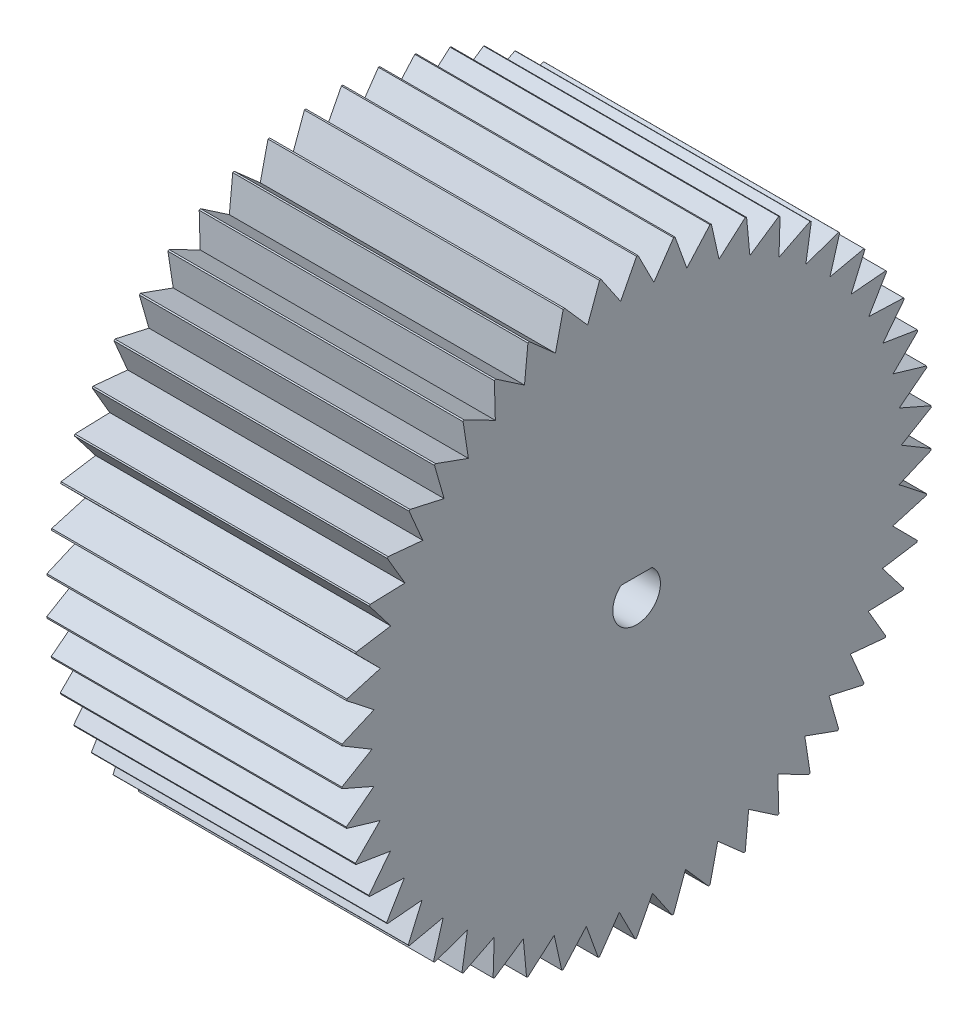
SolidWorks part; units mm, degrees
ref_plane "Front Plane" through (0, 0, 0) normal (0, 0, 1) x (1, 0, 0)
ref_plane "Top Plane" through (0, 0, 0) normal (0, 1, 0) x (1, 0, 0)
ref_plane "Right Plane" through (0, 0, 0) normal (1, 0, 0) x (0, 0, -1)
sketch "Sketch1" plane through (0, 0, 0) normal (1, 0, 0) x (0, 0, -1)
  line L0 (-3.0582, 25.2152) -> (-1.3735, 22.7329)
  line L1 (-1.3735, 22.7329) -> (0, 25.4)
  line L2 (0.1263, 25.3997) -> (1.4865, 22.7258)
  line L3 (1.4865, 22.7258) -> (3.1835, 25.1997)
  line L4 (3.3087, 25.1836) -> (4.3231, 22.3603)
  line L5 (4.3231, 22.3603) -> (6.3167, 24.602)
  line L6 (6.4389, 24.5703) -> (7.0915, 21.6421)
  line L7 (7.0915, 21.6421) -> (9.3504, 23.6163)
  line L8 (9.4676, 23.5696) -> (9.748, 20.5827)
  line L9 (9.748, 20.5827) -> (12.2365, 22.2582)
  line L10 (12.347, 22.1971) -> (12.2509, 19.1986)
  line L11 (12.2509, 19.1986) -> (14.9297, 20.549)
  line L12 (15.0317, 20.4746) -> (14.5605, 17.5118)
  line L13 (14.5605, 17.5118) -> (17.3875, 18.5158)
  line L14 (17.4793, 18.4291) -> (16.6405, 15.5488)
  line L15 (16.6405, 15.5488) -> (19.571, 16.1906)
  line L16 (19.6513, 16.0931) -> (18.4581, 13.3406)
  line L17 (18.4581, 13.3406) -> (21.4459, 13.61)
  line L18 (21.5133, 13.5032) -> (19.9845, 10.922)
  line L19 (19.9845, 10.922) -> (22.9826, 10.8148)
  line L20 (23.0361, 10.7004) -> (21.1958, 8.3311)
  line L21 (21.1958, 8.3311) -> (24.1568, 7.849)
  line L22 (24.1956, 7.7289) -> (22.0729, 5.6089)
  line L23 (22.0729, 5.6089) -> (24.9501, 4.7595)
  line L24 (24.9734, 4.6354) -> (22.6018, 2.7982)
  line L25 (22.6018, 2.7982) -> (25.3499, 1.5949)
  line L26 (25.3575, 1.4689) -> (22.7743, -0.0566)
  line L27 (22.7743, -0.0566) -> (25.3499, -1.5949)
  line L28 (25.3416, -1.7209) -> (22.5876, -2.9105)
  line L29 (22.5876, -2.9105) -> (24.9501, -4.7595)
  line L30 (24.9261, -4.8834) -> (22.0447, -5.7186)
  line L31 (22.0447, -5.7186) -> (24.1568, -7.849)
  line L32 (24.1175, -7.969) -> (21.1542, -8.4364)
  line L33 (21.1542, -8.4364) -> (22.9826, -10.8148)
  line L34 (22.9286, -10.9289) -> (19.93, -11.0212)
  line L35 (19.93, -11.0212) -> (21.4459, -13.61)
  line L36 (21.378, -13.7164) -> (18.3915, -13.4322)
  line L37 (18.3915, -13.4322) -> (19.571, -16.1906)
  line L38 (19.4903, -16.2877) -> (16.563, -15.6313)
  line L39 (16.563, -15.6313) -> (17.3875, -18.5158)
  line L40 (17.2952, -18.602) -> (14.4733, -17.584)
  line L41 (14.4733, -17.584) -> (14.9297, -20.549)
  line L42 (14.8274, -20.623) -> (12.1553, -19.2593)
  line L43 (12.1553, -19.2593) -> (12.2365, -22.2582)
  line L44 (12.1258, -22.3187) -> (9.6456, -20.6309)
  line L45 (9.6456, -20.6309) -> (9.3504, -23.6163)
  line L46 (9.2329, -23.6625) -> (6.9838, -21.6771)
  line L47 (6.9838, -21.6771) -> (6.3167, -24.602)
  line L48 (6.1944, -24.6331) -> (4.2119, -22.3815)
  line L49 (4.2119, -22.3815) -> (3.1835, -25.1997)
  line L50 (3.0582, -25.2152) -> (1.3735, -22.7329)
  line L51 (1.3735, -22.7329) -> (0, -25.4)
  line L52 (-0.1263, -25.3997) -> (-1.4865, -22.7258)
  line L53 (-1.4865, -22.7258) -> (-3.1835, -25.1997)
  line L54 (-3.3087, -25.1836) -> (-4.3231, -22.3603)
  line L55 (-4.3231, -22.3603) -> (-6.3167, -24.602)
  line L56 (-6.4389, -24.5703) -> (-7.0915, -21.6421)
  line L57 (-7.0915, -21.6421) -> (-9.3504, -23.6163)
  line L58 (-9.4676, -23.5696) -> (-9.748, -20.5827)
  line L59 (-9.748, -20.5827) -> (-12.2365, -22.2582)
  line L60 (-12.347, -22.1971) -> (-12.2509, -19.1986)
  line L61 (-12.2509, -19.1986) -> (-14.9297, -20.549)
  line L62 (-15.0317, -20.4746) -> (-14.5605, -17.5118)
  line L63 (-14.5605, -17.5118) -> (-17.3875, -18.5158)
  line L64 (-17.4793, -18.4291) -> (-16.6405, -15.5488)
  line L65 (-16.6405, -15.5488) -> (-19.571, -16.1906)
  line L66 (-19.6513, -16.0931) -> (-18.4581, -13.3406)
  line L67 (-18.4581, -13.3406) -> (-21.4459, -13.61)
  line L68 (-21.5133, -13.5032) -> (-19.9845, -10.922)
  line L69 (-19.9845, -10.922) -> (-22.9826, -10.8148)
  line L70 (-23.0361, -10.7004) -> (-21.1958, -8.3311)
  line L71 (-21.1958, -8.3311) -> (-24.1568, -7.849)
  line L72 (-24.1956, -7.7289) -> (-22.0729, -5.6089)
  line L73 (-22.0729, -5.6089) -> (-24.9501, -4.7595)
  line L74 (-24.9734, -4.6354) -> (-22.6018, -2.7982)
  line L75 (-22.6018, -2.7982) -> (-25.3499, -1.5949)
  line L76 (-25.3575, -1.4689) -> (-22.7743, 0.0566)
  line L77 (-22.7743, 0.0566) -> (-25.3499, 1.5949)
  line L78 (-25.3416, 1.7209) -> (-22.5876, 2.9105)
  line L79 (-22.5876, 2.9105) -> (-24.9501, 4.7595)
  line L80 (-24.9261, 4.8834) -> (-22.0447, 5.7186)
  line L81 (-22.0447, 5.7186) -> (-24.1568, 7.849)
  line L82 (-24.1175, 7.969) -> (-21.1542, 8.4364)
  line L83 (-21.1542, 8.4364) -> (-22.9826, 10.8148)
  line L84 (-22.9286, 10.9289) -> (-19.93, 11.0212)
  line L85 (-19.93, 11.0212) -> (-21.4459, 13.61)
  line L86 (-21.378, 13.7164) -> (-18.3915, 13.4322)
  line L87 (-18.3915, 13.4322) -> (-19.571, 16.1906)
  line L88 (-19.4903, 16.2877) -> (-16.563, 15.6313)
  line L89 (-16.563, 15.6313) -> (-17.3875, 18.5158)
  line L90 (-17.2952, 18.602) -> (-14.4733, 17.584)
  line L91 (-14.4733, 17.584) -> (-14.9297, 20.549)
  line L92 (-14.8274, 20.623) -> (-12.1553, 19.2593)
  line L93 (-12.1553, 19.2593) -> (-12.2365, 22.2582)
  line L94 (-12.1258, 22.3187) -> (-9.6456, 20.6309)
  line L95 (-9.6456, 20.6309) -> (-9.3504, 23.6163)
  line L96 (-9.2329, 23.6625) -> (-6.9838, 21.6771)
  line L97 (-6.9838, 21.6771) -> (-6.3167, 24.602)
  line L98 (-6.1944, 24.6331) -> (-4.2119, 22.3815)
  line L99 (-4.2119, 22.3815) -> (-3.1835, 25.1997)
  line L100 (-1.3416, 1.55) -> (1.3416, 1.55)
  arc A0 (-3.0582, 25.2152) -> (-3.1835, 25.1997) centre (0, 0) ccw
  arc A1 (-6.1944, 24.6331) -> (-6.3167, 24.602) centre (0, 0) ccw
  arc A2 (-9.2329, 23.6625) -> (-9.3504, 23.6163) centre (0, 0) ccw
  arc A3 (-12.1258, 22.3187) -> (-12.2365, 22.2582) centre (0, 0) ccw
  arc A4 (-14.8274, 20.623) -> (-14.9297, 20.549) centre (0, 0) ccw
  arc A5 (-17.2952, 18.602) -> (-17.3875, 18.5158) centre (0, 0) ccw
  arc A6 (-19.4903, 16.2877) -> (-19.571, 16.1906) centre (0, 0) ccw
  arc A7 (-21.378, 13.7164) -> (-21.4459, 13.61) centre (0, 0) ccw
  arc A8 (-22.9286, 10.9289) -> (-22.9826, 10.8148) centre (0, 0) ccw
  arc A9 (-24.1175, 7.969) -> (-24.1568, 7.849) centre (0, 0) ccw
  arc A10 (-24.9261, 4.8834) -> (-24.9501, 4.7595) centre (0, 0) ccw
  arc A11 (-25.3416, 1.7209) -> (-25.3499, 1.5949) centre (0, 0) ccw
  arc A12 (-25.3575, -1.4689) -> (-25.3499, -1.5949) centre (0, 0) ccw
  arc A13 (0.1263, 25.3997) -> (0, 25.4) centre (0, 0) ccw
  arc A14 (3.3087, 25.1836) -> (3.1835, 25.1997) centre (0, 0) ccw
  arc A15 (6.4389, 24.5703) -> (6.3167, 24.602) centre (0, 0) ccw
  arc A16 (9.4676, 23.5696) -> (9.3504, 23.6163) centre (0, 0) ccw
  arc A17 (12.347, 22.1971) -> (12.2365, 22.2582) centre (0, 0) ccw
  arc A18 (15.0317, 20.4746) -> (14.9297, 20.549) centre (0, 0) ccw
  arc A19 (17.4793, 18.4291) -> (17.3875, 18.5158) centre (0, 0) ccw
  arc A20 (19.6513, 16.0931) -> (19.571, 16.1906) centre (0, 0) ccw
  arc A21 (21.5133, 13.5032) -> (21.4459, 13.61) centre (0, 0) ccw
  arc A22 (23.0361, 10.7004) -> (22.9826, 10.8148) centre (0, 0) ccw
  arc A23 (24.1956, 7.7289) -> (24.1568, 7.849) centre (0, 0) ccw
  arc A24 (24.9734, 4.6354) -> (24.9501, 4.7595) centre (0, 0) ccw
  arc A25 (25.3575, 1.4689) -> (25.3499, 1.5949) centre (0, 0) ccw
  arc A26 (25.3416, -1.7209) -> (25.3499, -1.5949) centre (0, 0) ccw
  arc A27 (24.9261, -4.8834) -> (24.9501, -4.7595) centre (0, 0) ccw
  arc A28 (24.1175, -7.969) -> (24.1568, -7.849) centre (0, 0) ccw
  arc A29 (22.9286, -10.9289) -> (22.9826, -10.8148) centre (0, 0) ccw
  arc A30 (21.378, -13.7164) -> (21.4459, -13.61) centre (0, 0) ccw
  arc A31 (19.4903, -16.2877) -> (19.571, -16.1906) centre (0, 0) ccw
  arc A32 (17.2952, -18.602) -> (17.3875, -18.5158) centre (0, 0) ccw
  arc A33 (14.8274, -20.623) -> (14.9297, -20.549) centre (0, 0) ccw
  arc A34 (12.1258, -22.3187) -> (12.2365, -22.2582) centre (0, 0) ccw
  arc A35 (9.2329, -23.6625) -> (9.3504, -23.6163) centre (0, 0) ccw
  arc A36 (6.1944, -24.6331) -> (6.3167, -24.602) centre (0, 0) ccw
  arc A37 (3.0582, -25.2152) -> (3.1835, -25.1997) centre (0, 0) ccw
  arc A38 (-0.1263, -25.3997) -> (0, -25.4) centre (0, 0) ccw
  arc A39 (-3.3087, -25.1836) -> (-3.1835, -25.1997) centre (0, 0) ccw
  arc A40 (-6.4389, -24.5703) -> (-6.3167, -24.602) centre (0, 0) ccw
  arc A41 (-9.4676, -23.5696) -> (-9.3504, -23.6163) centre (0, 0) ccw
  arc A42 (-12.347, -22.1971) -> (-12.2365, -22.2582) centre (0, 0) ccw
  arc A43 (-15.0317, -20.4746) -> (-14.9297, -20.549) centre (0, 0) ccw
  arc A44 (-17.4793, -18.4291) -> (-17.3875, -18.5158) centre (0, 0) ccw
  arc A45 (-19.6513, -16.0931) -> (-19.571, -16.1906) centre (0, 0) ccw
  arc A46 (-21.5133, -13.5032) -> (-21.4459, -13.61) centre (0, 0) ccw
  arc A47 (-23.0361, -10.7004) -> (-22.9826, -10.8148) centre (0, 0) ccw
  arc A48 (-24.1956, -7.7289) -> (-24.1568, -7.849) centre (0, 0) ccw
  arc A49 (-24.9734, -4.6354) -> (-24.9501, -4.7595) centre (0, 0) ccw
  arc A50 (-1.3416, 1.55) -> (1.3416, 1.55) centre (0, 0) ccw
  point P156 (0, 0)
  dimension "D1" = 50.8
  dimension "D5" = 4.1
  dimension "D2" = 3
  dimension "D3" = 3
  dimension "D6" = 1.55
  dimension "D4" = 50
extrude "Boss-Extrude1" add sketch "Sketch1" along normal blind 25.4
